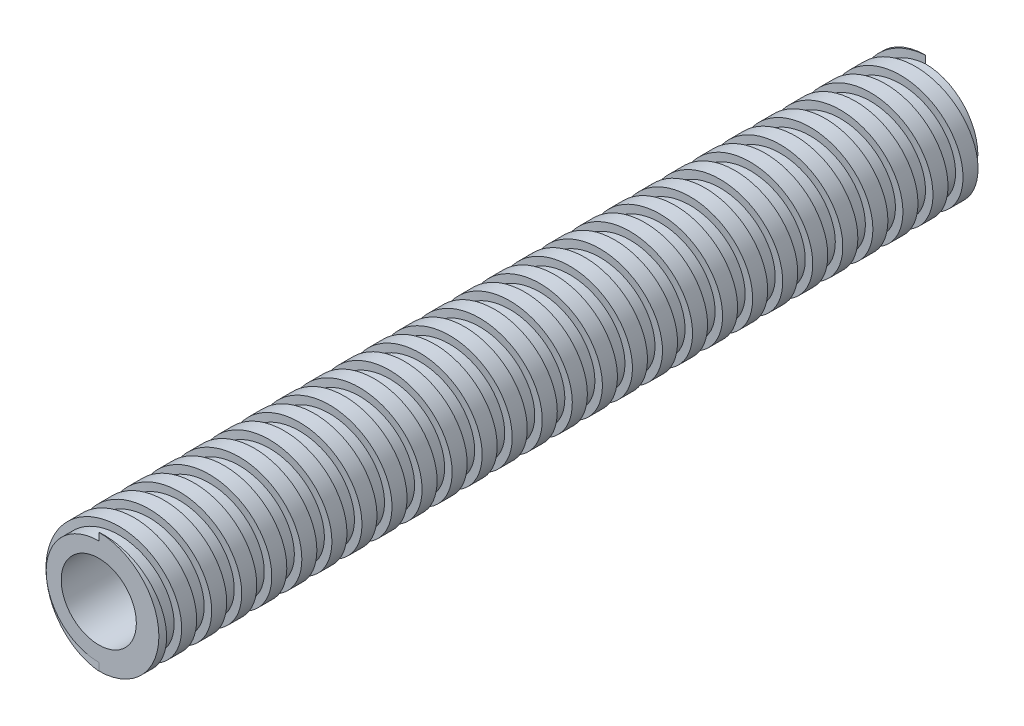
SolidWorks part; units mm, degrees
ref_plane "Front Plane" through (0, 0, 0) normal (0, 0, 1) x (1, 0, 0)
ref_plane "Top Plane" through (0, 0, 0) normal (0, 1, 0) x (1, 0, 0)
ref_plane "Right Plane" through (0, 0, 0) normal (1, 0, 0) x (0, 0, -1)
sketch "Sketch1" plane through (0, 0, 0) normal (0, 0, 1) x (1, 0, 0)
  circle A0 centre (0, 0) radius 4
  dimension "D1" = 8
extrude "Boss-Extrude1" add sketch "Sketch1" along normal blind 55
sketch "Sketch2" plane through (0, 0, 0) normal (1, 0, 0) x (0, 0, -1)
  line L1 (-1, 4) -> (0, 4)
  line L2 (-1, 4) -> (-1, 3.5)
  line L3 (-1, 3.5) -> (0, 3.5)
  line L4 (0, 4) -> (0, 3.5)
  dimension "D1" = 0.5
  dimension "D2" = 1
  dimension "D3" = 4
  dimension "D4" = 0
sketch "Sketch3" plane through (0, 0, 0) normal (0, 0, -1) x (-1, 0, 0)
  circle A0 centre (0, 0) radius 4 construction
  circle A1 centre (0, 0) radius 4
curve "Helix/Spiral1" pitch 2 height 55 turns 27.5
ref_plane "Plane2" through (4, 0, 0) normal (0, 0.9968, 0.0793) x (1, 0, 0)
sweep "Cut-Sweep1" cut profiles "Sketch2" path "Helix/Spiral1" align with end faces yes
sketch "Sketch4" plane through (0, 0, 0) normal (0, 0, -1) x (-1, 0, 0)
  circle A0 centre (0, 0) radius 2.5
  dimension "D1" = 5
sketch "Sketch6" plane through (0, 0, 55) normal (0, 0, 1) x (1, 0, 0)
  circle A0 centre (0, 0) radius 2.5
  point P0 (0, 0)
  dimension "D1" = 5
extrude "Cut-Extrude1" cut sketch "Sketch6" against normal blind 10
